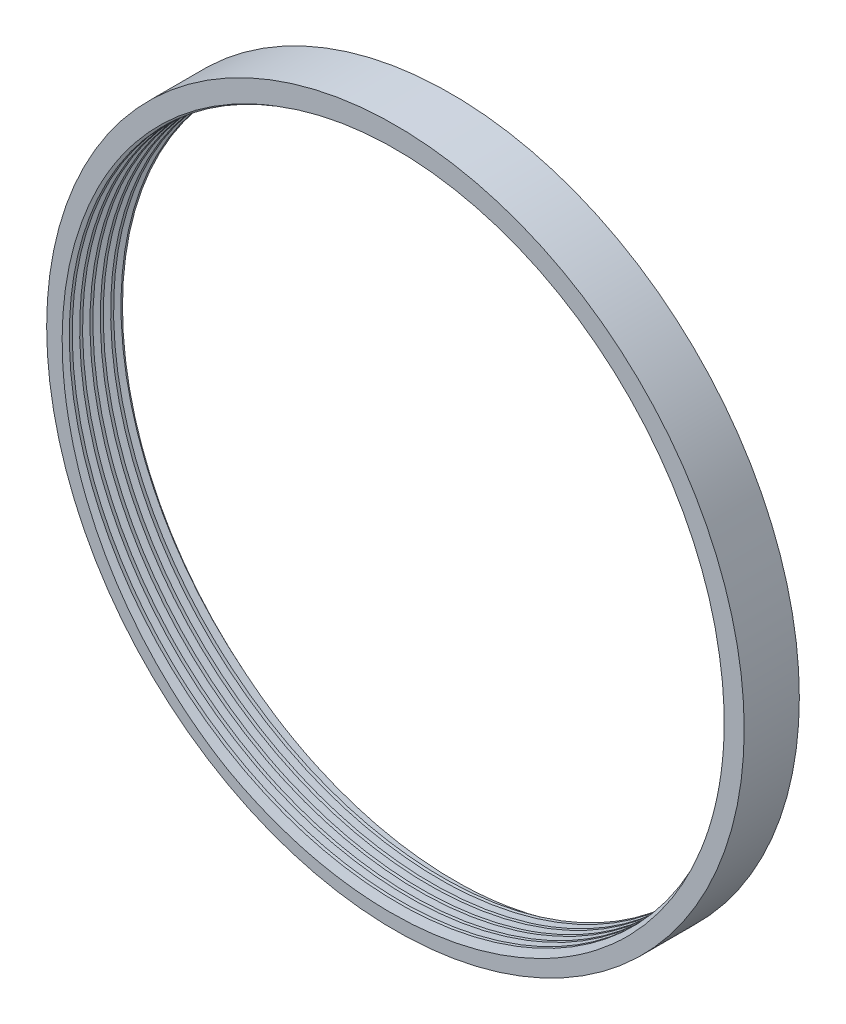
SolidWorks part; units mm, degrees
ref_plane "Front Plane" through (0, 0, 0) normal (0, 0, 1) x (1, 0, 0)
ref_plane "Top Plane" through (0, 0, 0) normal (0, 1, 0) x (1, 0, 0)
ref_plane "Right Plane" through (0, 0, 0) normal (1, 0, 0) x (0, 0, -1)
ref_plane "Plane1" through (0, 0, -1) normal (0, 0, 1) x (1, 0, 0)
sketch "Sketch1" plane through (0, 0, 0) normal (0, 0, 1) x (1, 0, 0)
  circle A0 centre (0, 0) radius 23.8
  circle A1 centre (0, 0) radius 25.3
  dimension "D1" = 47.6
  dimension "D2" = 1.5
extrude "Boss-Extrude1" add sketch "Sketch1" along normal blind 4
sketch "Sketch8" plane through (0, 0, -1) normal (0, 0, 1) x (1, 0, 0)
  circle A0 centre (0, 0) radius 23.8 construction
  circle A1 centre (0, 0) radius 23.8
curve "Helix/Spiral1" pitch 0.75 height 7.5 radius 23.8 left hand yes centre (0, 0, -1) axis (0, 0, 1) start towards (1, 0, 0)
sketch "Sketch9" plane through (0, 0, 0) normal (0, 1, 0) x (1, 0, 0)
  line L0 (23.8, 0.2683) -> (23.8, -0.2683)
  line L1 (23.8, -0.2683) -> (24.5, 0)
  line L2 (24.5, 0) -> (23.8, 0.2683)
  line L3 (25.3, 0) -> (-25.3, 0) construction
  dimension "D1" = 0.7
sweep "Cut-Sweep1" cut profiles "Sketch9" path "Helix/Spiral1" align with end faces yes
